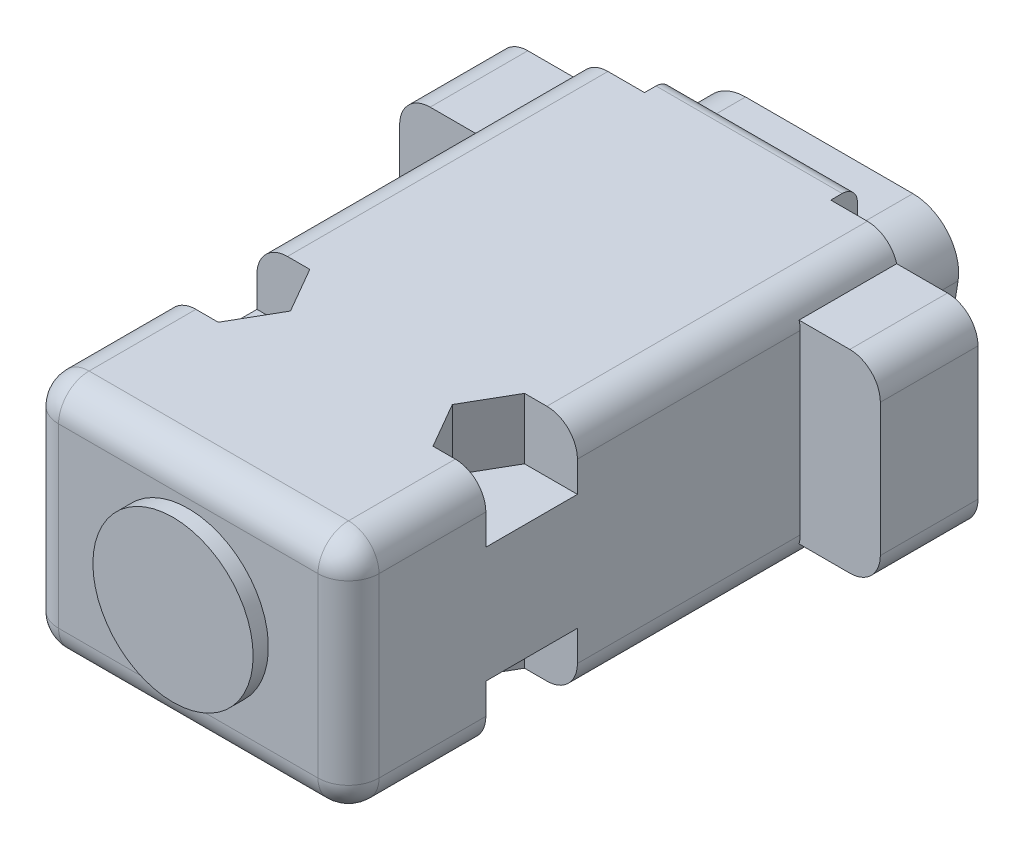
SolidWorks part; units mm, degrees
ref_plane "前视基准面" through (0, 0, 0) normal (0, 0, 1) x (1, 0, 0)
ref_plane "上视基准面" through (0, 0, 0) normal (0, 1, 0) x (1, 0, 0)
ref_plane "右视基准面" through (0, 0, 0) normal (1, 0, 0) x (0, 0, -1)
sketch "草图1" plane through (0, 0, 0) normal (0, 1, 0) x (1, 0, 0)
  line L0 (-6.1, 18) -> (-10.5, 18)
  line L1 (10.5, -18) -> (-10.5, -18)
  line L2 (10.5, -18) -> (10.5, 18)
  line L3 (10.5, 18) -> (6.1, 18)
  line L4 (-10.5, -18) -> (-10.5, 18)
  line L5 (10.5, -18) -> (-10.5, 18) construction
  line L6 (10.5, 18) -> (-10.5, -18) construction
  line L7 (6.1, 16.25) -> (-6.1, 16.25) construction
  line L8 (6.1, 18) -> (6.1, 19.75)
  line L9 (6.1, 19.75) -> (-6.1, 19.75)
  line L10 (-6.1, 18) -> (-6.1, 19.75)
  line L11 (6.1, 16.25) -> (-6.1, 19.75) construction
  line L12 (6.1, 19.75) -> (-6.1, 16.25) construction
  line L13 (-6.1, 18) -> (6.1, 18) construction
  point P0 (0, 0)
  point P6 (0, 18)
  dimension "D1" = 21
  dimension "D2" = 36
  dimension "D3" = 12.2
  dimension "D4" = 3.5
extrude "凸台-拉伸1" add sketch "草图1" along normal mid plane 15.6
sketch "草图3" plane through (0, 0, 18) normal (0, 0, 1) x (1, 0, 0)
  circle A0 centre (0, 0) radius 5.25
  dimension "D1" = 10.5
extrude "凸台-拉伸2" add sketch "草图3" along normal blind 1
sketch "草图5" plane through (0, 0, 0) normal (0, 1, 0) x (1, 0, 0)
  line L0 (10.5, 18) -> (6.1, 18) construction
  line L1 (15.75, 11.6) -> (-15.75, 11.6)
  line L2 (15.75, 11.6) -> (15.75, 18)
  line L3 (15.75, 18) -> (-15.75, 18)
  line L4 (-15.75, 11.6) -> (-15.75, 18)
  line L5 (15.75, 11.6) -> (-15.75, 18) construction
  line L6 (15.75, 18) -> (-15.75, 11.6) construction
  point P0 (0, 14.8)
  dimension "D1" = 31.5
  dimension "D2" = 6.4
extrude "凸台-拉伸3" add sketch "草图5" along normal mid plane 12.7
sketch "草图6" plane through (0, 0, -18) normal (0, 0, -1) x (-1, 0, 0)
  line L0 (-9, 4.8599) -> (9, 4.8599)
  line L1 (9, 4.8599) -> (7.5, -4.5401)
  line L2 (7.5, -4.5401) -> (-7.5, -4.5401)
  line L3 (-7.5, -4.5401) -> (-9, 4.8599)
  line L4 (9, 4.8599) -> (-7.5, -4.5401) construction
  line L5 (-9, 4.8599) -> (7.5, -4.5401) construction
  point P2 (0, -0.2674)
  dimension "D1" = 9.4
  dimension "D2" = 18
  dimension "D3" = 15
extrude "凸台-拉伸4" add sketch "草图6" along normal blind 6
fillet "圆角1" radius 3 4 edges at (-7.5, -4.5401, -21) (7.5, -4.5401, -21) (9, 4.8599, -21) (-9, 4.8599, -21)
fillet "圆角2" radius 2 12 edges at (0, -7.8, 18) (10.5, 0, 18) (0, 7.8, 18) (-10.5, 0, 18) (-10.5, -7.8, 0) (-10.5, 7.8, 0) (10.5, 7.8, 0) (10.5, -7.8, 0) (15.75, -6.35, -14.8) (15.75, 6.35, -14.8) (-15.75, 6.35, -14.8) (-15.75, -6.35, -14.8)
fillet "圆角3" radius 1 2 edges at (0, -7.8, -19.75) (0, 7.8, -19.75)
sketch "草图7" plane through (0, 7.8, 0) normal (0, 1, 0) x (1, 0, 0)
  line L0 (-10.5, -16) -> (-10.5, 11.6) construction
  line L1 (-12.2321, -6) -> (-10.5, -9)
  line L2 (-10.5, -9) -> (-7.0359, -9)
  line L3 (-7.0359, -9) -> (-5.3038, -6)
  line L4 (-5.3038, -6) -> (-7.0359, -3)
  line L5 (-7.0359, -3) -> (-10.5, -3)
  line L6 (-10.5, -3) -> (-12.2321, -6)
  line L8 (0, 0) -> (0, -9.484) construction
  line L9 (8.5, -18) -> (-8.5, -18) construction
  line L10 (10.5, -3) -> (12.2321, -6)
  line L11 (7.0359, -3) -> (10.5, -3)
  line L12 (5.3038, -6) -> (7.0359, -3)
  line L13 (7.0359, -9) -> (5.3038, -6)
  line L14 (10.5, -9) -> (7.0359, -9)
  line L15 (12.2321, -6) -> (10.5, -9)
  circle A0 centre (-8.7679, -6) radius 3 construction
  circle A1 centre (8.7679, -6) radius 3 construction
  dimension "D1" = 6
  dimension "D2" = 12
extrude "切除-拉伸1" cut sketch "草图7" against normal blind 4
mirror "镜向1" about plane through (0, 0, 0) normal (0, 1, 0) of "切除-拉伸1"
